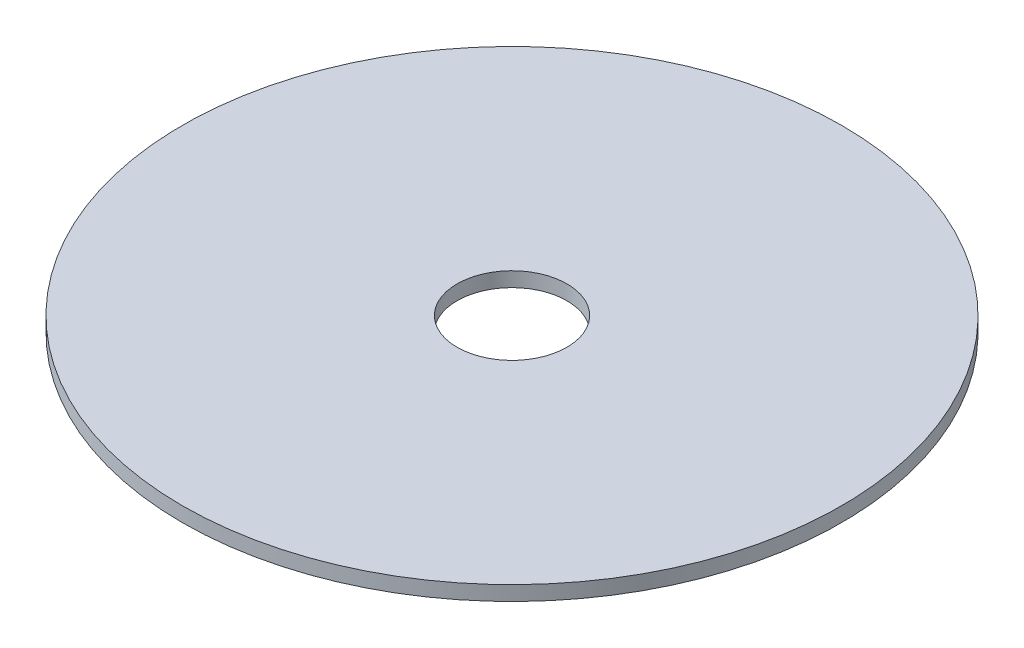
SolidWorks part; units mm, degrees
ref_plane "Front Plane" through (0, 0, 0) normal (0, 0, 1) x (1, 0, 0)
ref_plane "Top Plane" through (0, 0, 0) normal (0, 1, 0) x (1, 0, 0)
ref_plane "Right Plane" through (0, 0, 0) normal (1, 0, 0) x (0, 0, -1)
sketch "Sketch1" plane through (0, 0, 0) normal (0, 1, 0) x (1, 0, 0)
  circle A0 centre (0, 0) radius 90
  dimension "FLANGE_OD" = 180
extrude "Boss-Extrude1" add sketch "Sketch1" along normal blind 4
sketch "Sketch2" plane through (0, 0, 0) normal (0, 1, 0) x (1, 0, 0)
  circle A0 centre (0, 0) radius 15
  dimension "BORE_D" = 30
extrude "Cut-Extrude1" cut sketch "Sketch2" along normal through all
sketch "Sketch3" plane through (0, 4, 0) normal (0, 1, 0) x (1, 0, 0)
  circle A0 centre (0, 0) radius 10.7956 construction
  circle A1 centre (-10.7956, 0) radius 2.3001
  dimension "BOLT_D" = 4.6003
  dimension "BOLT_PCD" = 21.5913
extrude "Cut-Extrude2" cut sketch "Sketch3" against normal blind 2.9305 rebuild error yes
pattern_circular "CirPattern1" count 6 over 360 rebuild error yes
